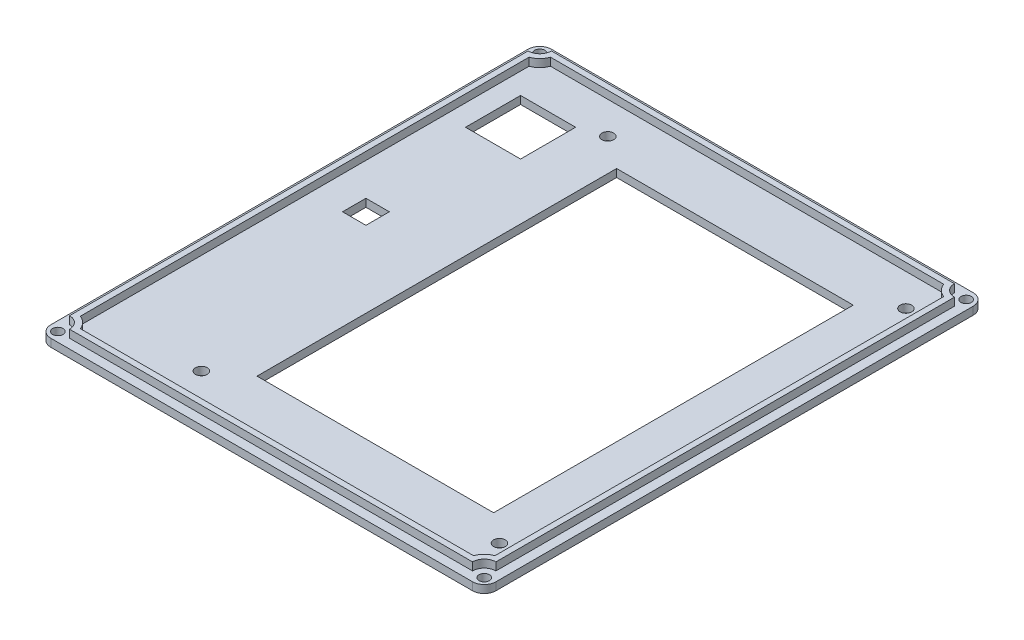
SolidWorks part; units mm, degrees
ref_plane "Front Plane" through (0, 0, 0) normal (0, 0, 1) x (1, 0, 0)
ref_plane "Top Plane" through (0, 0, 0) normal (0, 1, 0) x (1, 0, 0)
ref_plane "Right Plane" through (0, 0, 0) normal (1, 0, 0) x (0, 0, -1)
sketch "Sketch20" plane through (0, 0, 0) normal (0, 1, 0) x (1, 0, 0)
  line L0 (2.572, 21.812) -> (89.948, 21.812)
  line L1 (-2, 128.336) -> (94.52, 128.336)
  line L2 (-2, 128.336) -> (-2, 19.78)
  line L3 (-2, 19.78) -> (94.52, 19.78)
  line L4 (94.52, 128.336) -> (94.52, 19.78)
  line L5 (0.032, 123.764) -> (0.032, 24.352)
  line L10 (2.572, 126.304) -> (89.948, 126.304)
  line L11 (92.488, 123.764) -> (92.488, 24.352)
  line L15 (3.6241, 23.082) -> (88.8959, 23.082)
  line L16 (1.302, 122.7119) -> (1.302, 25.4041)
  line L17 (3.6241, 125.034) -> (88.8959, 125.034)
  line L18 (91.218, 122.7119) -> (91.218, 25.4041)
  arc A0 (0.032, 123.764) -> (2.572, 126.304) centre (0.032, 126.304) ccw
  arc A1 (0.032, 24.352) -> (2.572, 21.812) centre (0.032, 21.812) cw
  arc A2 (89.948, 126.304) -> (92.488, 123.764) centre (92.488, 126.304) ccw
  arc A3 (89.948, 21.812) -> (92.488, 24.352) centre (92.488, 21.812) cw
  arc A5 (1.302, 122.7119) -> (3.6241, 125.034) centre (0.032, 126.304) ccw
  arc A6 (1.302, 25.4041) -> (3.6241, 23.082) centre (0.032, 21.812) cw
  arc A7 (88.8959, 125.034) -> (91.218, 122.7119) centre (92.488, 126.304) ccw
  arc A8 (88.8959, 23.082) -> (91.218, 25.4041) centre (92.488, 21.812) cw
  dimension "D21" = 2.54
  dimension "D22" = 2.54
  dimension "D23" = 2.54
  dimension "D24" = 2.54
  dimension "D30" = 1.27
  dimension "D31" = 3.81
  dimension "D32" = 3.81
  dimension "D33" = 3.81
  dimension "D28" = 3.81
  dimension "D2" = 108.556
  dimension "D4" = 96.52
  dimension "D7" = 2.032
  dimension "D8" = 2.032
  dimension "D9" = 2.032
  dimension "D10" = 2.032
  dimension "D13" = 4.572
  dimension "D14" = 4.572
  dimension "D15" = 4.572
  dimension "D16" = 4.572
  dimension "D17" = 4.572
  dimension "D18" = 4.572
  dimension "D19" = 4.572
  dimension "D20" = 4.572
  dimension "D25" = 1.27
  dimension "D26" = 1.27
  dimension "D27" = 1.27
extrude "Boss-Extrude5" add sketch "Sketch20" against normal blind 1.7 separate body contours L4 L3 L2 L1
extrude "Boss-Extrude6" add sketch "Sketch20<3>" along normal blind 1.7 contours L17 A7 L18 A8 L15 A6 L16 A5 | L10 A2 L11 A3 L0 A1 L5 A0
sketch "Sketch20<3>" plane through (0, 0, 0) normal (0, 1, 0) x (1, 0, 0) same geometry as "Sketch20"
fillet "Fillet3" radius 2.54 4 edges at (-2, -0.85, -19.78) (-2, -0.85, -128.336) (94.52, -0.85, -128.336) (94.52, -0.85, -19.78)
hole_wizard "#4-40 Tapped Hole3" positions "Sketch27" profile "Sketch25" tap size "#4-40" standard "ANSI Inch" end condition through all
sketch "Sketch27" plane through (0, 0, 0) normal (0, 1, 0) x (1, 0, 0)
  point P0 (0.032, 21.812)
  point P3 (92.488, 21.812)
  point P6 (92.488, 126.304)
  point P9 (0.032, 126.304)
sketch "Sketch25" plane through (0.032, 0, -21.812) normal (1, 0, 0) x (0, 0, 1)
  line L0 (0, 0) -> (0, 1.7)
  line L1 (0, 1.7) -> (1.1303, 1.7)
  line L2 (1.1303, 1.7) -> (1.1303, 0)
  line L5 (1.1303, 0) -> (0, 0)
  line L11 (0, -6.35) -> (0, 107.95) construction
  dimension "Thru Tap Drill Dia." = 2.2606
  dimension "Thru Tap Drill Depth" = 1.7
cosmetic thread "Hole Thread15" parameters "D2"=2.8448
cosmetic thread "Hole Thread16" parameters "D2"=2.8448
cosmetic thread "Hole Thread17" parameters "D2"=2.8448
cosmetic thread "Hole Thread18" parameters "D2"=2.8448
sketch "Sketch28" plane through (0, -1.7, 0) normal (0, -1, 0) x (1, 0, 0)
  line L1 (90.202, -27.4) -> (3.334, -27.4)
  line L2 (90.202, -27.4) -> (90.202, -120.618)
  line L3 (90.202, -120.618) -> (3.334, -120.618)
  line L4 (3.334, -27.4) -> (3.334, -120.618)
  line L5 (20.479, -27.4) -> (20.479, -120.618) construction
  line L6 (81.312, -35.02) -> (30.004, -35.02)
  line L7 (81.312, -35.02) -> (81.312, -112.998)
  line L8 (81.312, -112.998) -> (30.004, -112.998)
  line L9 (30.004, -35.02) -> (30.004, -112.998)
  line L10 (0.54, -19.78) -> (91.98, -19.78) construction
  line L11 (17.812, -104.362) -> (5.874, -104.362)
  line L12 (17.812, -104.362) -> (17.812, -116.3)
  line L13 (17.812, -116.3) -> (5.874, -116.3)
  line L14 (5.874, -104.362) -> (5.874, -116.3)
  line L15 (13.494, -75.152) -> (8.414, -75.152)
  line L16 (13.494, -75.152) -> (13.494, -80.232)
  line L17 (13.494, -80.232) -> (8.414, -80.232)
  line L18 (8.414, -75.152) -> (8.414, -80.232)
  line L19 (-2, -125.796) -> (-2, -22.32) construction
  line L20 (0.54, -128.336) -> (91.98, -128.336) construction
  circle A0 centre (87.662, -29.94) radius 1.27
  circle A1 centre (87.662, -118.078) radius 1.27
  circle A2 centre (23.019, -29.94) radius 1.27
  circle A3 centre (23.019, -118.078) radius 1.27
  dimension "D3" = 2.54
  dimension "D4" = 2.54
  dimension "D5" = 2.54
  dimension "D6" = 2.54
  dimension "D1" = 86.868
  dimension "D2" = 93.218
  dimension "D7" = 2.54
  dimension "D8" = 2.54
  dimension "D9" = 2.54
  dimension "D10" = 2.54
  dimension "D11" = 17.145
  dimension "D12" = 2.54
  dimension "D13" = 2.54
  dimension "D14" = 2.54
  dimension "D15" = 51.308
  dimension "D16" = 77.978
  dimension "D17" = 7.62
  dimension "D18" = 2.54
  dimension "D19" = 9.525
  dimension "D20" = 5.08
  dimension "D21" = 5.08
  dimension "D22" = 5.08
  dimension "D23" = 4.318
  dimension "D24" = 11.938
  dimension "D25" = 11.938
  dimension "D26" = 2.54
  dimension "D27" = 24.13
  dimension "D28" = 7.62
  dimension "D29" = 7.718
  dimension "D30" = 5.334
extrude "Cut-Extrude1" cut sketch "Sketch28" against normal blind 8.89 contours L11 L14 L13 L12 | L15 L18 L17 L16 | L7 L8 L9 L6 | A1 | A0 | A3 | A2 region at (11.843, -1.7, -110.331) region at (10.954, -1.7, -77.692)
